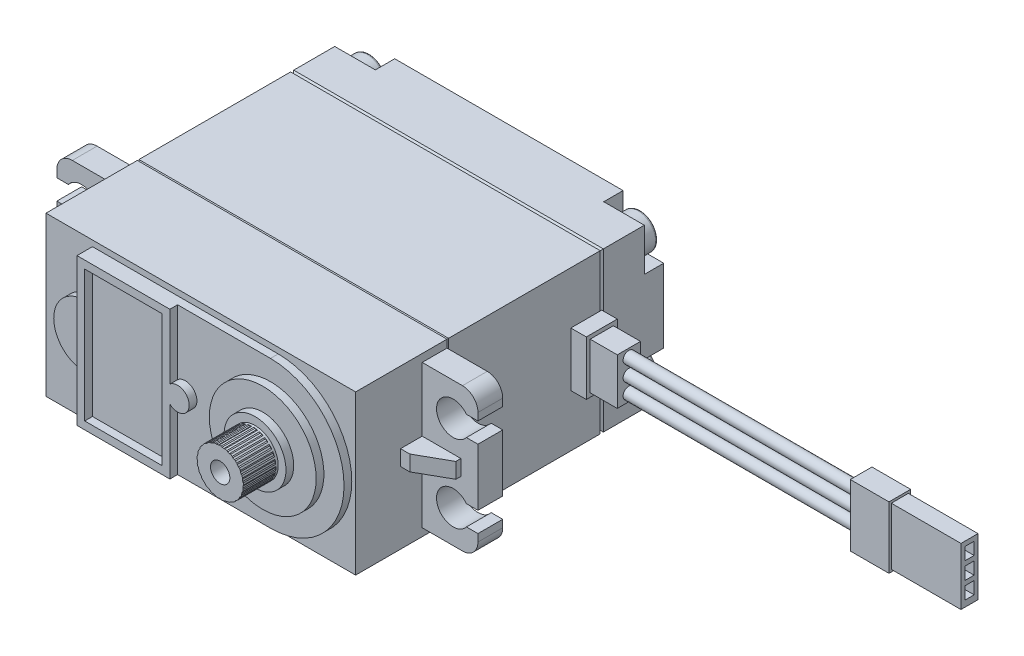
SolidWorks part; units mm, degrees
ref_plane "前视基准面" through (0, 0, 0) normal (0, 0, 1) x (1, 0, 0)
ref_plane "上视基准面" through (0, 0, 0) normal (0, 1, 0) x (1, 0, 0)
ref_plane "右视基准面" through (0, 0, 0) normal (1, 0, 0) x (0, 0, -1)
sketch "草图1" plane through (0, 0, 0) normal (0, 0, 1) x (1, 0, 0)
  line L1 (-20, 10.25) -> (20, 10.25)
  line L2 (-20, 10.25) -> (-20, -10.25)
  line L3 (-20, -10.25) -> (20, -10.25)
  line L4 (20, 10.25) -> (20, -10.25)
  dimension "D1" = 10.25
  dimension "D2" = 20.5
  dimension "D3" = 20
  dimension "D4" = 40
extrude "凸台-拉伸1" add sketch "草图1" along normal blind 8
chamfer "倒角1" distance 0.2 angle 45 4 edges at (0, 10.25, 8) (20, 0, 8) (0, -10.25, 8) (-20, 0, 8)
sketch "草图2" plane through (0, 0, 8) normal (0, 0, 1) x (1, 0, 0)
  line L0 (20, 10.25) -> (20, -10.25) construction
  line L1 (20, -10.25) -> (-20, -10.25) construction
  line L2 (-20, -10.25) -> (-20, 10.25) construction
  line L3 (-20, 10.25) -> (20, 10.25) construction
  line L4 (20, 10.25) -> (20, -10.25)
  line L5 (20, -10.25) -> (-20, -10.25)
  line L6 (-20, -10.25) -> (-20, 10.25)
  line L7 (-20, 10.25) -> (20, 10.25)
extrude "凸台-拉伸2" add sketch "草图2" along normal blind 20
chamfer "倒角4" distance 0.2 angle 45 4 edges at (-20, 0, 8) (0, 10.25, 8) (20, 0, 8) (0, -10.25, 8)
chamfer "倒角5" distance 0.2 angle 45 4 edges at (20, 0, 28) (0, -10.25, 28) (-20, 0, 28) (0, 10.25, 28)
sketch "草图3" plane through (0, 0, 28) normal (0, 0, 1) x (1, 0, 0)
  line L0 (20, 10.25) -> (20, -10.25) construction
  line L1 (20, -10.25) -> (-20, -10.25) construction
  line L2 (-20, -10.25) -> (-20, 10.25) construction
  line L3 (-20, 10.25) -> (20, 10.25) construction
  line L4 (20, 10.25) -> (20, -10.25)
  line L5 (20, -10.25) -> (-20, -10.25)
  line L6 (-20, -10.25) -> (-20, 10.25)
  line L7 (-20, 10.25) -> (20, 10.25)
extrude "凸台-拉伸3" add sketch "草图3" along normal blind 12.8
sketch "草图4" plane through (0, 0, 40.8) normal (0, 0, 1) x (1, 0, 0)
  line L0 (20, -10.25) -> (20, 10.25) construction
  circle A0 centre (10, 0) radius 6.9
  dimension "D1" = 10
  dimension "D2" = 13.8
extrude "凸台-拉伸4" add sketch "草图4" along normal blind 2
sketch "草图5" plane through (0, 0, 42.8) normal (0, 0, 1) x (1, 0, 0)
  circle A0 centre (10, 0) radius 3
  dimension "D1" = 6
extrude "凸台-拉伸5" add sketch "草图5" along normal blind 4.5
ref_plane "基准面1" through (0, 0, 28) normal (0, 0, 1) x (1, 0, 0)
sketch "草图8" plane through (0, 0, 28) normal (0, 0, 1) x (1, 0, 0)
  line L4 (-20, 10.25) -> (-20, -10.25) construction
  line L5 (-27.2, 9.25) -> (-27.2, 6.3)
  line L6 (20, -9.25) -> (27.2, -9.25)
  line L7 (-20, 9.25) -> (-20, -9.25)
  line L8 (-20, -9.25) -> (-27.2, -9.25)
  line L9 (-20, 9.25) -> (-27.2, 9.25)
  line L10 (27.2, -6.3) -> (27.2, -9.25)
  line L12 (25.7125, -6.3) -> (27.2, -6.3)
  line L13 (25.7125, -3.7) -> (27.2, -3.7)
  line L14 (-25.7125, 6.3) -> (-27.2, 6.3)
  line L15 (-25.7125, 3.7) -> (-27.2, 3.7)
  line L16 (-27.2, 3.7) -> (-27.2, -3.7)
  line L17 (27.2, 3.7) -> (27.2, -3.7)
  line L18 (-25.7125, -3.7) -> (-27.2, -3.7)
  line L19 (25.7125, 3.7) -> (27.2, 3.7)
  line L20 (-25.7125, -6.3) -> (-27.2, -6.3)
  line L21 (-27.2, -6.3) -> (-27.2, -9.25)
  line L22 (25.7125, 6.3) -> (27.2, 6.3)
  line L23 (27.2, 9.25) -> (27.2, 6.3)
  line L24 (20, 9.25) -> (20, -9.25)
  line L25 (20, 9.25) -> (27.2, 9.25)
  arc A0 (-25.7125, 3.7) -> (-25.7125, 6.3) centre (-24, 5) ccw
  arc A1 (-25.7125, -3.7) -> (-25.7125, -6.3) centre (-24, -5) cw
  arc A2 (25.7125, -3.7) -> (25.7125, -6.3) centre (24, -5) ccw
  arc A3 (25.7125, 3.7) -> (25.7125, 6.3) centre (24, 5) cw
  point P11 (-27.2, 10.25)
  point P12 (-27.2, -10.25)
  point P19 (-19.0859, 9.25)
  point P20 (-30.2671, 9.25)
  point P29 (-24, 6.3)
  point P31 (-29.7758, 6.3)
  point P32 (-24, 3.7)
  point P33 (-29.7758, 3.7)
  dimension "D5" = 4.3
extrude "凸台-拉伸6" add sketch "草图8" along normal blind 3.2
sketch "草图9" plane through (0, 0, 31.2) normal (0, 0, 1) x (1, 0, 0)
  line L5 (-25, -1) -> (-20, -1)
  line L6 (-25, 1) -> (-20, 1)
  line L7 (-20, -9.25) -> (-20, 9.25) construction
  line L8 (-20, -1) -> (-20, 1)
  line L10 (-25, -1) -> (-25, 1)
  line L12 (25, -1) -> (25, 1)
  line L13 (25, -1) -> (20, -1)
  line L14 (20, -1) -> (20, 1)
  line L15 (25, 1) -> (20, 1)
  line L18 (-20, -9.25) -> (-20, 9.25) construction
  line L19 (-25, -9.25) -> (-25, 9.25) construction
  point P0 (-27.2, 0)
  point P1 (-27.2, -1)
  point P2 (0.4483, -1)
  point P3 (0.4483, 0)
  point P6 (-27.2, 1)
  point P7 (0.4483, 1)
extrude "凸台-拉伸7" add sketch "草图9" along normal blind 2.8
sketch "草图10" plane through (0, -1, 0) normal (0, -1, 0) x (1, 0, 0)
  line L0 (-25, 31.8565) -> (-21.193, 34)
  line L1 (-25, 34) -> (-25, 31.2) construction
  line L2 (-25, 34) -> (-20, 34) construction
  line L3 (-21.193, 34) -> (-25, 34)
  line L4 (-25, 34) -> (-25, 31.8565)
  line L7 (25, 34) -> (25, 31.8565)
  line L8 (25, 31.8565) -> (21.193, 34)
  line L9 (21.193, 34) -> (25, 34)
extrude "切除-拉伸6" cut sketch "草图10" against normal blind 2.8
sketch "草图11" plane through (0, 0, 47.3) normal (0, 0, 1) x (1, 0, 0)
  circle A0 centre (10, 0) radius 1.25
  dimension "D1" = 2.5
extrude "切除-拉伸7" cut sketch "草图11" against normal blind 6
sketch "草图12" plane through (0, 0, 47.3) normal (0, 0, 1) x (1, 0, 0)
  line L1 (9.7425, 2.9387) -> (9.88, 2.9976)
  line L2 (10.2575, 2.9387) -> (10.12, 2.9976)
  line L3 (10.9802, 2.7824) -> (10.8617, 2.8736)
  line L4 (10.4815, 2.9104) -> (10.6292, 2.9333)
  line L5 (11.6414, 2.4512) -> (11.5493, 2.569)
  line L6 (11.1901, 2.6993) -> (11.3389, 2.6846)
  line L7 (12.1994, 1.966) -> (12.1395, 2.103)
  line L8 (11.824, 2.3185) -> (11.9645, 2.2673)
  line L9 (12.6192, 1.3573) -> (12.5953, 1.5049)
  line L10 (12.3433, 1.792) -> (12.4667, 1.7075)
  line L11 (12.8745, 0.6633) -> (12.888, 0.8122)
  line L12 (12.7154, 1.153) -> (12.8138, 1.0404)
  line L13 (12.9491, -0.0724) -> (12.9992, 0.0685)
  line L14 (12.9168, 0.4415) -> (12.9841, 0.308)
  line L15 (12.8384, -0.8036) -> (12.922, -0.6796)
  line L16 (12.9349, -0.2978) -> (12.967, -0.4438)
  line L17 (12.5494, -1.4842) -> (12.6612, -1.3849)
  line L18 (12.7687, -1.0183) -> (12.7634, -1.1677)
  line L19 (12.1002, -2.0716) -> (12.2332, -2.0032)
  line L20 (12.4284, -1.6749) -> (12.3862, -1.8183)
  line L21 (11.5191, -2.5288) -> (11.6649, -2.4956)
  line L22 (11.9356, -2.2262) -> (11.859, -2.3546)
  line L23 (10.8424, -2.8272) -> (10.9919, -2.8313)
  line L24 (11.3212, -2.6376) -> (11.2151, -2.7429)
  line L25 (10.1129, -2.9478) -> (10.2566, -2.989)
  line L26 (10.6237, -2.8833) -> (10.4948, -2.9589)
  line L27 (9.3763, -2.8833) -> (9.5052, -2.9589)
  line L28 (9.8871, -2.9478) -> (9.7434, -2.989)
  line L29 (8.6788, -2.6376) -> (8.7849, -2.7429)
  line L30 (9.1576, -2.8272) -> (9.0081, -2.8313)
  line L31 (8.0644, -2.2262) -> (8.141, -2.3546)
  line L32 (8.4809, -2.5288) -> (8.3351, -2.4956)
  line L33 (7.5716, -1.6749) -> (7.6138, -1.8183)
  line L34 (7.8998, -2.0716) -> (7.7668, -2.0032)
  line L35 (7.2313, -1.0183) -> (7.2366, -1.1677)
  line L36 (7.4506, -1.4842) -> (7.3388, -1.3849)
  line L37 (7.0651, -0.2978) -> (7.033, -0.4438)
  line L38 (7.1616, -0.8036) -> (7.078, -0.6796)
  line L39 (7.0832, 0.4415) -> (7.0159, 0.308)
  line L40 (7.0509, -0.0724) -> (7.0008, 0.0685)
  line L41 (7.2846, 1.153) -> (7.1862, 1.0404)
  line L42 (7.1255, 0.6633) -> (7.112, 0.8122)
  line L43 (7.6567, 1.792) -> (7.5333, 1.7075)
  line L44 (7.3808, 1.3573) -> (7.4047, 1.5049)
  line L45 (8.176, 2.3185) -> (8.0355, 2.2673)
  line L46 (7.8006, 1.966) -> (7.8605, 2.103)
  line L47 (8.8099, 2.6993) -> (8.6611, 2.6846)
  line L48 (8.3586, 2.4512) -> (8.4507, 2.569)
  line L49 (9.5185, 2.9104) -> (9.3708, 2.9333)
  line L50 (9.0198, 2.7824) -> (9.1383, 2.8736)
  arc A0 (9.7425, 2.9387) -> (9.5185, 2.9104) centre (10, 0) ccw
  arc A1 (9.0198, 2.7824) -> (8.8099, 2.6993) centre (10, 0) ccw
  circle A2 centre (10, 0) radius 3 construction
  arc A3 (9.88, 2.9976) -> (9.3708, 2.9333) centre (10, 0) ccw
  arc A4 (9.1383, 2.8736) -> (8.6611, 2.6846) centre (10, 0) ccw
  arc A5 (8.3586, 2.4512) -> (8.176, 2.3185) centre (10, 0) ccw
  arc A6 (8.4507, 2.569) -> (8.0355, 2.2673) centre (10, 0) ccw
  arc A7 (7.8006, 1.966) -> (7.6567, 1.792) centre (10, 0) ccw
  arc A8 (7.8605, 2.103) -> (7.5333, 1.7075) centre (10, 0) ccw
  arc A9 (7.3808, 1.3573) -> (7.2846, 1.153) centre (10, 0) ccw
  arc A10 (7.4047, 1.5049) -> (7.1862, 1.0404) centre (10, 0) ccw
  arc A11 (7.1255, 0.6633) -> (7.0832, 0.4415) centre (10, 0) ccw
  arc A12 (7.112, 0.8122) -> (7.0159, 0.308) centre (10, 0) ccw
  arc A13 (7.0509, -0.0724) -> (7.0651, -0.2978) centre (10, 0) ccw
  arc A14 (7.0008, 0.0685) -> (7.033, -0.4438) centre (10, 0) ccw
  arc A15 (7.1616, -0.8036) -> (7.2313, -1.0183) centre (10, 0) ccw
  arc A16 (7.078, -0.6796) -> (7.2366, -1.1677) centre (10, 0) ccw
  arc A17 (7.3388, -1.3849) -> (7.6138, -1.8183) centre (10, 0) ccw
  arc A18 (7.4506, -1.4842) -> (7.5716, -1.6749) centre (10, 0) ccw
  arc A19 (7.8998, -2.0716) -> (8.0644, -2.2262) centre (10, 0) ccw
  arc A20 (7.7668, -2.0032) -> (8.141, -2.3546) centre (10, 0) ccw
  arc A21 (8.4809, -2.5288) -> (8.6788, -2.6376) centre (10, 0) ccw
  arc A22 (8.3351, -2.4956) -> (8.7849, -2.7429) centre (10, 0) ccw
  arc A23 (9.1576, -2.8272) -> (9.3763, -2.8833) centre (10, 0) ccw
  arc A24 (9.0081, -2.8313) -> (9.5052, -2.9589) centre (10, 0) ccw
  arc A25 (9.8871, -2.9478) -> (10.1129, -2.9478) centre (10, 0) ccw
  arc A26 (9.7434, -2.989) -> (10.2566, -2.989) centre (10, 0) ccw
  arc A27 (10.6237, -2.8833) -> (10.8424, -2.8272) centre (10, 0) ccw
  arc A28 (10.4948, -2.9589) -> (10.9919, -2.8313) centre (10, 0) ccw
  arc A29 (11.3212, -2.6376) -> (11.5191, -2.5288) centre (10, 0) ccw
  arc A30 (11.2151, -2.7429) -> (11.6649, -2.4956) centre (10, 0) ccw
  arc A31 (11.9356, -2.2262) -> (12.1002, -2.0716) centre (10, 0) ccw
  arc A32 (11.859, -2.3546) -> (12.2332, -2.0032) centre (10, 0) ccw
  arc A33 (12.3862, -1.8183) -> (12.6612, -1.3849) centre (10, 0) ccw
  arc A34 (12.4284, -1.6749) -> (12.5494, -1.4842) centre (10, 0) ccw
  arc A35 (12.7634, -1.1677) -> (12.922, -0.6796) centre (10, 0) ccw
  arc A36 (12.7687, -1.0183) -> (12.8384, -0.8036) centre (10, 0) ccw
  arc A37 (12.967, -0.4438) -> (12.9992, 0.0685) centre (10, 0) ccw
  arc A38 (12.9349, -0.2978) -> (12.9491, -0.0724) centre (10, 0) ccw
  arc A39 (12.9841, 0.308) -> (12.888, 0.8122) centre (10, 0) ccw
  arc A40 (12.9168, 0.4415) -> (12.8745, 0.6633) centre (10, 0) ccw
  arc A41 (12.7154, 1.153) -> (12.6192, 1.3573) centre (10, 0) ccw
  arc A42 (12.8138, 1.0404) -> (12.5953, 1.5049) centre (10, 0) ccw
  arc A43 (12.3433, 1.792) -> (12.1994, 1.966) centre (10, 0) ccw
  arc A44 (12.4667, 1.7075) -> (12.1395, 2.103) centre (10, 0) ccw
  arc A45 (11.824, 2.3185) -> (11.6414, 2.4512) centre (10, 0) ccw
  arc A46 (11.9645, 2.2673) -> (11.5493, 2.569) centre (10, 0) ccw
  arc A47 (11.1901, 2.6993) -> (10.9802, 2.7824) centre (10, 0) ccw
  arc A48 (11.3389, 2.6846) -> (10.8617, 2.8736) centre (10, 0) ccw
  arc A49 (10.4815, 2.9104) -> (10.2575, 2.9387) centre (10, 0) ccw
  arc A50 (10.6292, 2.9333) -> (10.12, 2.9976) centre (10, 0) ccw
  point P111 (10, 0)
  dimension "D1" = 5.9
  dimension "D4" = 25
extrude "切除-拉伸8" cut sketch "草图12" against normal blind 4.2
sketch "草图13" plane through (0, 0, 40.8) normal (0, 0, 1) x (1, 0, 0)
  line L0 (10, 9.5) -> (-14, 9.5)
  line L1 (10, -9.5) -> (-14, -9.5)
  line L2 (20, -10.25) -> (20, 10.25) construction
  line L5 (-20, -10.25) -> (20, -10.25) construction
  line L6 (-14, 9.5) -> (-14, -9.5)
  line L7 (-20, 10.25) -> (-20, -10.25) construction
  line L8 (20, 10.25) -> (-20, 10.25) construction
  line L9 (20, -10.25) -> (20, 10.25)
  line L10 (-20, -10.25) -> (20, -10.25)
  line L11 (-20, 10.25) -> (-20, -10.25)
  line L12 (20, 10.25) -> (-20, 10.25)
  arc A0 (10, -9.5) -> (10, 9.5) centre (10, 0) ccw
  point P15 (-14, 10.25)
  point P16 (-14, -11.4768)
  dimension "D1" = 19
extrude "切除-拉伸9" cut sketch "草图13" against normal blind 1
fillet "圆角1" radius 2 4 edges at (27.2, 9.25, 29.6) (27.2, -9.25, 29.6) (-27.2, 9.25, 29.6) (-27.2, -9.25, 29.6)
sketch "草图17" plane through (20, 0, 0) normal (1, 0, 0) x (0, 0, -1)
  line L2 (-12, 3.5) -> (-8, 3.5)
  line L3 (-12, 3.5) -> (-12, -3.5)
  line L4 (-12, -3.5) -> (-8, -3.5)
  line L5 (-8, 3.5) -> (-8, -3.5)
  dimension "D2" = 7
  dimension "D3" = 3.5
  dimension "D4" = 4
extrude "凸台-拉伸8" add sketch "草图17" along normal blind 2
sketch "草图18" plane through (22, 0, 0) normal (1, 0, 0) x (0, 0, -1)
  line L8 (-11.5, 3) -> (-11.5, -3)
  line L9 (-11.5, -3) -> (-8.5, -3)
  line L10 (-8.5, -3) -> (-8.5, 3)
  line L11 (-8.5, 3) -> (-11.5, 3)
  line L12 (-11.5, 3) -> (-11.5, -3)
  line L13 (-11.5, -3) -> (-8.5, -3)
  line L14 (-8.5, -3) -> (-8.5, 3)
  line L15 (-8.5, 3) -> (-11.5, 3)
  dimension "D1" = 0.5
extrude "凸台-拉伸9" add sketch "草图18" along normal blind 3.5
sketch "草图19" plane through (25.5, 0, 0) normal (1, 0, 0) x (0, 0, -1)
  line L0 (-8.5, -3) -> (-8.5, 3) construction
  line L1 (-8.5, -3) -> (-8.5, 3) construction
  line L2 (-8.5, 3) -> (-11.5, 3) construction
  circle A0 centre (-10, 0) radius 0.75
  circle A1 centre (-10, 2) radius 0.75
  circle A2 centre (-10, -2) radius 0.75
  dimension "D1" = 1.5
  dimension "D2" = 1.5
  dimension "D3" = 1.5
  dimension "D4" = 1.5
  dimension "D5" = 1.5
  dimension "D6" = 1.5
  dimension "D7" = 1
  dimension "D8" = 2
  dimension "D9" = 2
extrude "凸台-拉伸10" add sketch "草图19" along normal blind 30
sketch "草图20" plane through (55.5, 0, 0) normal (1, 0, 0) x (0, 0, -1)
  line L1 (-11.4, 4) -> (-8.6, 4)
  line L2 (-11.4, 4) -> (-11.4, -4)
  line L3 (-11.4, -4) -> (-8.6, -4)
  line L4 (-8.6, 4) -> (-8.6, -4)
  circle A0 centre (-10, 2) radius 0.75 construction
  dimension "D1" = 8
  dimension "D2" = 2.8
  dimension "D3" = 1.4
  dimension "D4" = 4
extrude "凸台-拉伸11" add sketch "草图20" along normal blind 5
sketch "草图21" plane through (60.5, 0, 0) normal (1, 0, 0) x (0, 0, -1)
  line L5 (-10.59, 3.1) -> (-9.4, 3.1)
  line L6 (-10.59, 3.1) -> (-10.59, 1.5)
  line L7 (-10.59, 1.5) -> (-9.4, 1.5)
  line L8 (-11.1, 3.7) -> (-11.1, -3.7)
  line L9 (-11.1, -3.7) -> (-8.9, -3.7)
  line L10 (-8.9, -3.7) -> (-8.9, 3.7)
  line L11 (-8.9, 3.7) -> (-11.1, 3.7)
  line L12 (-11.1, 3.7) -> (-11.1, -3.7)
  line L13 (-11.1, -3.7) -> (-8.9, -3.7)
  line L14 (-8.9, -3.7) -> (-8.9, 3.7)
  line L15 (-8.9, 3.7) -> (-11.1, 3.7)
  line L16 (-9.4, 3.1) -> (-9.4, 1.5)
  line L17 (-10.59, 0.9) -> (-9.4, 0.9)
  line L18 (-10.59, 0.9) -> (-10.59, -0.7)
  line L19 (-10.59, -0.7) -> (-9.4, -0.7)
  line L20 (-9.4, 0.9) -> (-9.4, -0.7)
  line L21 (-10.59, -1.3) -> (-9.4, -1.3)
  line L22 (-10.59, -1.3) -> (-10.59, -2.9)
  line L23 (-10.59, -2.9) -> (-9.4, -2.9)
  line L24 (-9.4, -1.3) -> (-9.4, -2.9)
  dimension "D2" = 1.6
  dimension "D3" = 1.6
  dimension "D4" = 1.6
  dimension "D5" = 0.5
  dimension "D6" = 0.5
  dimension "D7" = 0.5
  dimension "D8" = 0.6
  dimension "D9" = 0.6
  dimension "D10" = 0.6
  dimension "D1" = 0.3
extrude "凸台-拉伸12" add sketch "草图21" along normal blind 9
sketch "草图22" plane through (0, 0, 0) normal (0, 0, -1) x (-1, 0, 0)
  line L5 (-20, 4.75) -> (-20, 10.25)
  line L6 (-20, 10.25) -> (-14.75, 10.25)
  line L7 (-17.5, -4.75) -> (-20, -4.75)
  line L8 (-14.75, -7.5) -> (-14.75, -10.25)
  line L9 (-20, -4.75) -> (-20, -10.25)
  line L11 (-20, -10.25) -> (-14.75, -10.25)
  line L12 (-14.75, 7.5) -> (-14.75, 10.25)
  line L13 (-17.5, 4.75) -> (-20, 4.75)
  line L14 (14.75, -7.5) -> (14.75, -10.25)
  line L15 (20, -10.25) -> (14.75, -10.25)
  line L16 (20, -4.75) -> (20, -10.25)
  line L17 (17.5, -4.75) -> (20, -4.75)
  line L18 (20, 4.75) -> (20, 10.25)
  line L19 (17.5, 4.75) -> (20, 4.75)
  line L20 (14.75, 7.5) -> (14.75, 10.25)
  line L21 (20, 10.25) -> (14.75, 10.25)
  arc A0 (-14.75, -7.5) -> (-17.5, -4.75) centre (-17.5, -7.5) ccw
  arc A1 (-14.75, 7.5) -> (-17.5, 4.75) centre (-17.5, 7.5) cw
  arc A2 (14.75, -7.5) -> (17.5, -4.75) centre (17.5, -7.5) cw
  arc A3 (14.75, 7.5) -> (17.5, 4.75) centre (17.5, 7.5) ccw
  dimension "D3" = 5.5
extrude "切除-拉伸13" cut sketch "草图22" against normal blind 2.5
sketch "草图23" plane through (0, 0, 2.5) normal (0, 0, -1) x (-1, 0, 0)
  line L4 (-17.25, -7.75) -> (-15.6165, -7.75)
  line L5 (-17.25, -7.25) -> (-15.6165, -7.25)
  line L6 (-17.25, 7.25) -> (-17.25, 5.6165)
  line L7 (-17.25, 7.75) -> (-15.6165, 7.75)
  line L8 (-17.25, -7.25) -> (-17.25, -5.6165)
  line L9 (-17.75, 7.25) -> (-17.75, 5.6165)
  line L10 (-17.75, -7.25) -> (-17.75, -5.6165)
  line L11 (-17.25, 7.25) -> (-15.6165, 7.25)
  line L12 (-19.3835, -7.25) -> (-17.75, -7.25)
  line L13 (-19.3835, -7.75) -> (-17.75, -7.75)
  line L14 (-17.75, -9.3835) -> (-17.75, -7.75)
  line L15 (-17.25, -9.3835) -> (-17.25, -7.75)
  line L16 (-19.3835, 7.25) -> (-17.75, 7.25)
  line L17 (-19.3835, 7.75) -> (-17.75, 7.75)
  line L18 (-17.25, 9.3835) -> (-17.25, 7.75)
  line L19 (-17.75, 9.3835) -> (-17.75, 7.75)
  line L20 (17.25, -7.25) -> (15.6165, -7.25)
  line L21 (17.25, -7.75) -> (15.6165, -7.75)
  line L22 (17.25, -9.3835) -> (17.25, -7.75)
  line L23 (17.75, -9.3835) -> (17.75, -7.75)
  line L24 (19.3835, -7.75) -> (17.75, -7.75)
  line L25 (19.3835, -7.25) -> (17.75, -7.25)
  line L26 (17.75, -7.25) -> (17.75, -5.6165)
  line L27 (17.25, -7.25) -> (17.25, -5.6165)
  line L28 (19.3835, 7.25) -> (17.75, 7.25)
  line L29 (17.75, 7.25) -> (17.75, 5.6165)
  line L30 (17.25, 7.25) -> (17.25, 5.6165)
  line L31 (17.25, 7.25) -> (15.6165, 7.25)
  line L32 (17.25, 7.75) -> (15.6165, 7.75)
  line L33 (17.25, 9.3835) -> (17.25, 7.75)
  line L34 (17.75, 9.3835) -> (17.75, 7.75)
  line L35 (19.3835, 7.75) -> (17.75, 7.75)
  circle A0 centre (-17.5, 7.5) radius 2.25
  arc A1 (-15.6165, 7.25) -> (-15.6165, 7.75) centre (-17.5, 7.5) ccw
  arc A2 (-17.75, 5.6165) -> (-17.25, 5.6165) centre (-17.5, 7.5) ccw
  arc A3 (-19.3835, 7.75) -> (-19.3835, 7.25) centre (-17.5, 7.5) ccw
  arc A4 (-17.25, 9.3835) -> (-17.75, 9.3835) centre (-17.5, 7.5) ccw
  arc A5 (-17.75, -5.6165) -> (-17.25, -5.6165) centre (-17.5, -7.5) cw
  arc A6 (-15.6165, -7.25) -> (-15.6165, -7.75) centre (-17.5, -7.5) cw
  arc A7 (-19.3835, -7.75) -> (-19.3835, -7.25) centre (-17.5, -7.5) cw
  arc A8 (-17.25, -9.3835) -> (-17.75, -9.3835) centre (-17.5, -7.5) cw
  circle A9 centre (-17.5, -7.5) radius 2.25
  arc A10 (15.6165, -7.25) -> (15.6165, -7.75) centre (17.5, -7.5) ccw
  arc A11 (17.25, -9.3835) -> (17.75, -9.3835) centre (17.5, -7.5) ccw
  arc A12 (19.3835, -7.75) -> (19.3835, -7.25) centre (17.5, -7.5) ccw
  arc A13 (17.75, -5.6165) -> (17.25, -5.6165) centre (17.5, -7.5) ccw
  circle A14 centre (17.5, -7.5) radius 2.25
  arc A15 (17.75, 5.6165) -> (17.25, 5.6165) centre (17.5, 7.5) cw
  arc A16 (19.3835, 7.75) -> (19.3835, 7.25) centre (17.5, 7.5) cw
  arc A17 (15.6165, 7.25) -> (15.6165, 7.75) centre (17.5, 7.5) cw
  arc A18 (17.25, 9.3835) -> (17.75, 9.3835) centre (17.5, 7.5) cw
  circle A19 centre (17.5, 7.5) radius 2.25
  point P8 (-19.75, 7.25)
  point P9 (-13.9428, 7.25)
  point P10 (-17.75, 9.75)
  point P11 (-17.75, 5.25)
  point P12 (-19.75, 7.75)
  point P13 (-13.9428, 7.75)
  point P14 (-17.25, 9.75)
  point P15 (-17.25, 5.25)
  dimension "D1" = 4.5
  dimension "D2" = 3.8
extrude "凸台-拉伸13" add sketch "草图23" along normal blind 2
fillet "圆角2" radius 0.3 4 edges at (-19.75, -7.5, 0.5) (19.75, -7.5, 0.5) (15.25, 7.5, 0.5) (-15.25, 7.5, 0.5)
sketch "草图25" plane through (0, 0, 40.8) normal (0, 0, 1) x (1, 0, 0)
  line L0 (-14, 9.5) -> (-14, -9.5) construction
  circle A0 centre (-14, 0) radius 4
  dimension "D1" = 8
extrude "凸台-拉伸15" add sketch "草图25" against normal blind 1
sketch "草图26" plane through (0, 0, 40.8) normal (0, 0, 1) x (1, 0, 0)
  line L0 (10, 9.5) -> (-14, 9.5) construction
  line L1 (-14, 9.5) -> (-2, 9.5)
  line L2 (-14, 9.5) -> (-14, -9.5)
  line L3 (-14, -9.5) -> (-2, -9.5)
  line L4 (-2, 9.5) -> (-2, -9.5)
  line L5 (-14, 9.5) -> (-14, 4) construction
  line L6 (-14, -9.5) -> (10, -9.5) construction
  line L7 (-13, 8.5) -> (-3, 8.5)
  line L8 (-3, 8.5) -> (-3, -8.5)
  line L9 (-13, -8.5) -> (-3, -8.5)
  line L10 (-13, 8.5) -> (-13, -8.5)
  dimension "D1" = 12
  dimension "D2" = 1
extrude "凸台-拉伸16" add sketch "草图26" along normal blind 1
sketch "草图27" plane through (0, 0, 42.8) normal (0, 0, 1) x (1, 0, 0)
  circle A0 centre (10, 0) radius 4
  circle A1 centre (10, 0) radius 6.9 construction
  circle A2 centre (10, 0) radius 6.9
  dimension "D1" = 8
extrude "切除-拉伸14" cut sketch "草图27" against normal blind 1
sketch "草图28" plane through (0, 0, 40.8) normal (0, 0, 1) x (1, 0, 0)
  circle A0 centre (-1, 0) radius 1.5
  circle A1 centre (10, 0) radius 3 construction
  dimension "D1" = 11
  dimension "D2" = 3
extrude "凸台-拉伸17" add sketch "草图28" along normal blind 1
